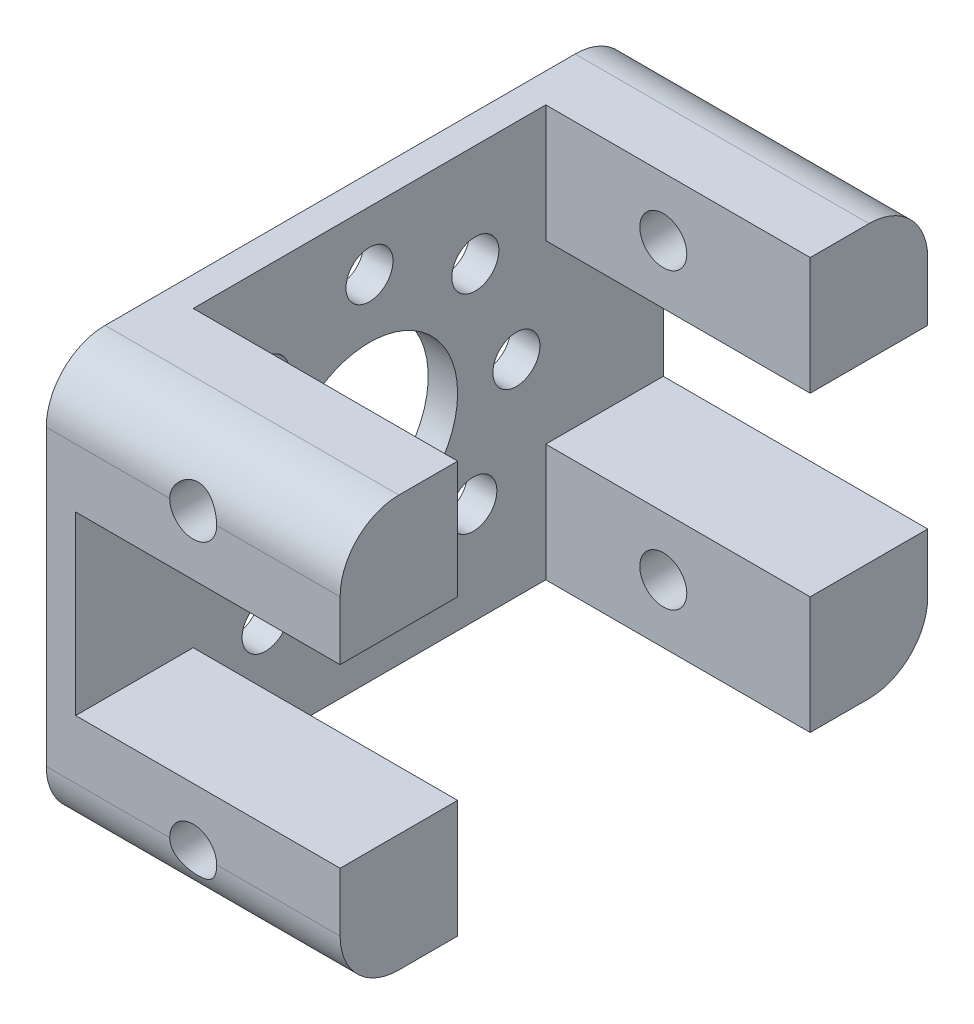
SolidWorks part; units mm, degrees
ref_plane "Plano frontal" through (0, 0, 0) normal (0, 0, 1) x (1, 0, 0)
ref_plane "Plano superior" through (0, 0, 0) normal (0, 1, 0) x (1, 0, 0)
ref_plane "Plano direito" through (0, 0, 0) normal (1, 0, 0) x (0, 0, -1)
sketch "Esboço1" plane through (0, 0, 0) normal (1, 0, 0) x (0, 0, -1)
  line L1 (-50, 35) -> (50, 35)
  line L2 (-50, 35) -> (-50, -35)
  line L3 (-50, -35) -> (50, -35)
  line L4 (50, 35) -> (50, -35)
  line L5 (-50, 35) -> (50, -35) construction
  line L6 (-50, -35) -> (50, 35) construction
  point P0 (0, 0)
  dimension "D1" = 100
  dimension "D2" = 70
extrude "Ressalto-extrusão1" add sketch "Esboço1" along normal blind 50 contours L2 L1 L4 L3
sketch "Esboço3" plane through (0, 0, 50) normal (0, 0, 1) x (1, 0, 0)
  line L0 (50, 35) -> (50, -35) construction
  line L1 (50, -15) -> (5, -15)
  line L2 (50, -15) -> (50, 15)
  line L3 (50, 15) -> (5, 15)
  line L4 (5, -15) -> (5, 15)
  point P6 (0, 0)
  dimension "D1" = 45
  dimension "D2" = 20
  dimension "D3" = 20
extrude "Corte-extrusão1" cut sketch "Esboço3" against normal through all contours L2 L1 L4 L3
sketch "Esboço4" plane through (0, -35, 0) normal (0, -1, 0) x (-1, 0, 0)
  line L0 (-50, -50) -> (-50, 50) construction
  line L1 (-50, 30) -> (-5, 30)
  line L2 (-50, 30) -> (-50, -30)
  line L3 (-50, -30) -> (-5, -30)
  line L4 (-5, 30) -> (-5, -30)
  dimension "D1" = 20
  dimension "D2" = 20
  dimension "D3" = 45
extrude "Corte-extrusão2" cut sketch "Esboço4" against normal through all contours L2 L1 L4 L3
sketch "Esboço5" plane through (0, 0, 0) normal (-1, 0, 0) x (0, 0, 1)
  circle A0 centre (0, 0) radius 15
  dimension "D1" = 30
extrude "Corte-extrusão3" cut sketch "Esboço5" against normal through all
sketch "Esboço6" plane through (0, 0, 0) normal (-1, 0, 0) x (0, 0, 1)
  circle A1 centre (25, 0) radius 4
  circle A2 centre (0, -25) radius 4
  circle A3 centre (-25, 0) radius 4
  circle A5 centre (17.6777, 17.6777) radius 4
  circle A6 centre (17.6777, -17.6777) radius 4
  circle A7 centre (-17.6777, -17.6777) radius 4
  circle A8 centre (0, 25) radius 4
  dimension "D1" = 8
extrude "Corte-extrusão4" cut sketch "Esboço6" against normal through all contours A3
extrude "Corte-extrusão5" cut sketch "Esboço6<3>" against normal blind 50 contours A7
sketch "Esboço6<3>" plane through (0, 0, 0) normal (-1, 0, 0) x (0, 0, 1) same geometry as "Esboço6"
extrude "Corte-extrusão6" cut sketch "Esboço6<4>" against normal blind 50 contours A2
sketch "Esboço6<4>" plane through (0, 0, 0) normal (-1, 0, 0) x (0, 0, 1) same geometry as "Esboço6"
extrude "Corte-extrusão7" cut sketch "Esboço6<5>" against normal blind 50 contours A6
sketch "Esboço6<5>" plane through (0, 0, 0) normal (-1, 0, 0) x (0, 0, 1) same geometry as "Esboço6"
extrude "Corte-extrusão8" cut sketch "Esboço6<6>" against normal blind 50 contours A1
sketch "Esboço6<6>" plane through (0, 0, 0) normal (-1, 0, 0) x (0, 0, 1) same geometry as "Esboço6"
extrude "Corte-extrusão9" cut sketch "Esboço6<7>" against normal blind 50 contours A5
sketch "Esboço6<7>" plane through (0, 0, 0) normal (-1, 0, 0) x (0, 0, 1) same geometry as "Esboço6"
extrude "Corte-extrusão10" cut sketch "Esboço6<8>" against normal blind 50 contours A8
sketch "Esboço6<8>" plane through (0, 0, 0) normal (-1, 0, 0) x (0, 0, 1) same geometry as "Esboço6"
sketch "Esboço8" plane through (0, 0, 0) normal (-1, 0, 0) x (0, 0, 1)
  circle A0 centre (-18.0185, 17.5611) radius 4
extrude "Corte-extrusão11" cut sketch "Esboço8" against normal blind 50
sketch "Esboço9" plane through (0, 0, 50) normal (0, 0, 1) x (1, 0, 0)
  circle A0 centre (25, -25) radius 4
  dimension "D1" = 8
extrude "Corte-extrusão12" cut sketch "Esboço9" against normal through all
sketch "Esboço10" plane through (0, 0, 50) normal (0, 0, 1) x (1, 0, 0)
  circle A0 centre (25, 25) radius 4
extrude "Corte-extrusão13" cut sketch "Esboço10" against normal through all
fillet "Filete2" radius 10 1 edges at (25, -35, 50)
fillet "Filete3" radius 10 1 edges at (25, 35, 50)
fillet "Filete4" radius 10 1 edges at (25, 35, -50)
fillet "Filete5" radius 10 1 edges at (25, -35, -50)
